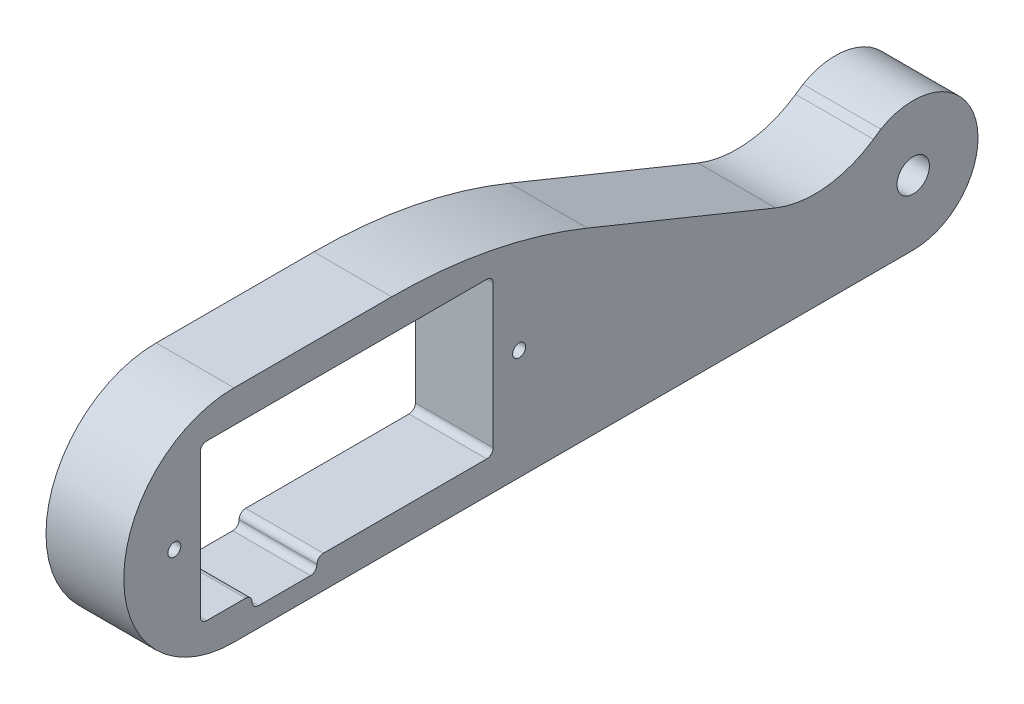
SolidWorks part; units mm, degrees
ref_plane "Piano frontale" through (0, 0, 0) normal (0, 0, 1) x (1, 0, 0)
ref_plane "Piano superiore" through (0, 0, 0) normal (0, 1, 0) x (1, 0, 0)
ref_plane "Piano destro" through (0, 0, 0) normal (1, 0, 0) x (0, 0, -1)
sketch "Schizzo1" plane through (0, 0, 0) normal (1, 0, 0) x (0, 0, -1)
  line L0 (2.6, 14.5) -> (22.6, 14.5)
  line L1 (0, 12) -> (22.6, 12)
  line L2 (0, 12) -> (0, 0)
  line L3 (0, 0) -> (22.6, 0)
  line L4 (22.6, 12) -> (22.6, 0)
  line L5 (22.6, 14.5) -> (48.3781, 4)
  line L6 (48.3781, 4) -> (52.5, 6.8301)
  line L7 (2.6, -2.5) -> (55, -2.5)
  line L9 (4, 0) -> (9, 0)
  line L10 (4, 0) -> (4, -1)
  line L11 (4, -1) -> (9, -1)
  line L12 (9, 0) -> (9, -1)
  circle A0 centre (55, 2.5) radius 5
  arc A2 (2.6, -2.5) -> (2.6, 14.5) centre (2.6, 6) cw
  circle A3 centre (55, 2.5) radius 1.25
  circle A4 centre (24.6, 6) radius 0.5
  circle A5 centre (-2, 6) radius 0.5
  point P23 (0, 6)
  dimension "D3" = 10
  dimension "D7" = 1.5
  dimension "D11" = 8.5
  dimension "D12" = 2.5
  dimension "D15" = 1
  dimension "D16" = 1
  dimension "D1" = 22.6
  dimension "D2" = 12
  dimension "D4" = 2.5
  dimension "D5" = 2.5
  dimension "D6" = 20
  dimension "D8" = 55
  dimension "D9" = 2.5
  dimension "D10" = 5
  dimension "D13" = 5
  dimension "D14" = 1
  dimension "D17" = 2
  dimension "D18" = 2
  dimension "D19" = 4
extrude "Estrusione-Estrusione1" add sketch "Schizzo1" along normal blind 6 contours A2 L7 A0 L6 L5 L0 A5 A4 L3 L12 L11 L10 L2 L1 L4 | A0 A3 region at (0, 4.5058, -24.3965) region at (0, 0.8803, -50.4194)
fillet "Raccordo1" radius 8 1 edges at (3, 4, -48.3781) type face fillet first side face at (3, 5.4151, -50.439) second side face at (3, 9.25, -35.489)
fillet "Raccordo2" radius 40 1 edges at (3, 14.5, -22.6) type face fillet first side face at (3, 14.5, -12.6) second side face at (3, 10.0631, -33.4929)
fillet "Raccordo3" radius 0.5 8 edges at (3, 0, -22.6) (3, 0, 0) (3, 12, 0) (3, 12, -22.6) (3, 0, -4) (3, -1, -4) (3, -1, -9) (3, 0, -9)
